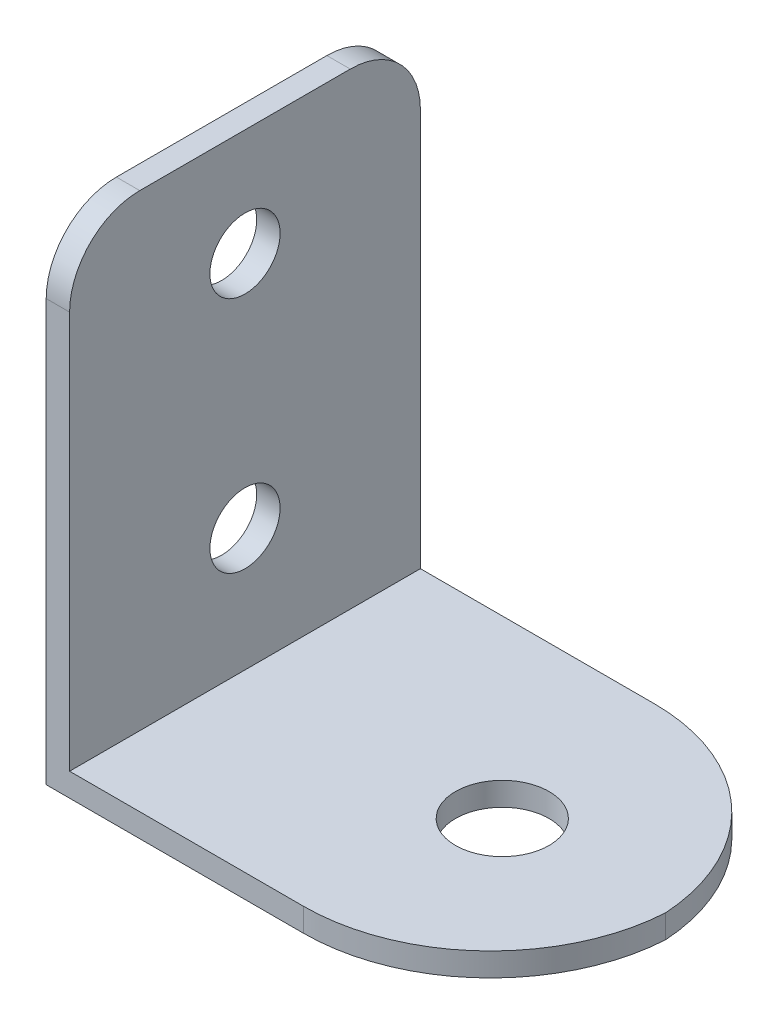
SolidWorks part; units mm, degrees
ref_plane "Front Plane" through (0, 0, 0) normal (0, 0, 1) x (1, 0, 0)
ref_plane "Top Plane" through (0, 0, 0) normal (0, 1, 0) x (1, 0, 0)
ref_plane "Right Plane" through (0, 0, 0) normal (1, 0, 0) x (0, 0, -1)
sketch "Sketch1" plane through (0, 0, 0) normal (0, 0, 1) x (1, 0, 0)
  line L0 (0, 0) -> (0, 20)
  line L1 (0, 0) -> (18, 0)
extrude "Extrude-Thin1" add sketch "Sketch1" along normal blind 15 thin thin type one direction wall 1
fillet "Fillet1" radius 8 2 edges at (18, -0.5, 0) (18, -0.5, 15)
sketch "Sketch2" plane through (-1, 0, 0) normal (-1, 0, 0) x (0, 0, 1)
  circle A0 centre (7.5, 5.2476) radius 1.5
  circle A1 centre (7.5, 15.4201) radius 1.5
extrude "Cut-Extrude1" cut sketch "Sketch2" against normal through all
fillet "Fillet2" radius 3 2 edges at (-0.5, 20, 15) (-0.5, 20, 0)
sketch "Sketch3" plane through (0, 0, 0) normal (0, 1, 0) x (1, 0, 0)
  line L0 (0, -15) -> (0, 0) construction
  circle A0 centre (11, -7.5) radius 2
  dimension "D1" = 11
extrude "Cut-Extrude2" cut sketch "Sketch3" against normal through all
